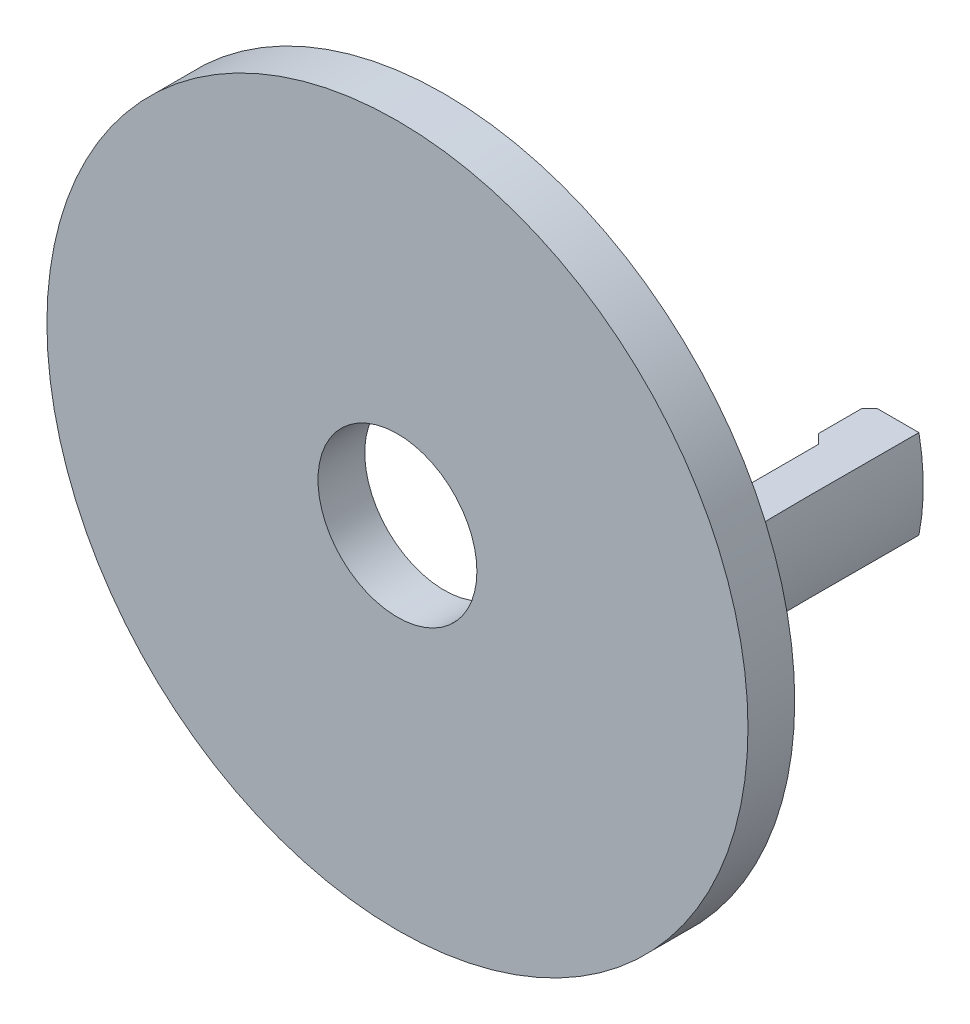
SolidWorks part; units mm, degrees
ref_plane "Front" through (0, 0, 0) normal (0, 0, 1) x (1, 0, 0)
ref_plane "Top" through (0, 0, 0) normal (0, 1, 0) x (1, 0, 0)
ref_plane "Right" through (0, 0, 0) normal (1, 0, 0) x (0, 0, -1)
sketch "Guard base sketch" plane through (0, 0, 0) normal (0, 0, 1) x (1, 0, 0)
  circle A0 centre (0, 0) radius 37.5
  dimension "D1" = 75
extrude "Guard" add sketch "Guard base sketch" along normal blind 5
sketch "Inner axle base sketch" plane through (0, 0, 5) normal (0, 0, 1) x (1, 0, 0)
  circle A0 centre (0, 0) radius 8.5
  dimension "D1" = 17
extrude "Inner axle hole" cut sketch "Inner axle base sketch" against normal through all
sketch "Coupling tooth base sketch" plane through (0, 0, 0) normal (0, 1, 0) x (1, 0, 0)
  line L0 (19.5, 0) -> (26, 0) construction
  line L1 (26, 0) -> (26, 27) construction
  line L2 (26, 0) -> (16.5, 0)
  line L3 (26, 27) -> (19.5, 27) construction
  line L4 (19.5, 27) -> (18, 25.5) construction
  line L5 (18, 21) -> (19.5, 19.5) construction
  line L6 (19.5, 19.5) -> (19.5, 0) construction
  line L7 (19.75, 20.3107) -> (19.75, 2.8964)
  line L8 (19.5, 3) -> (16.5, 0) construction
  line L9 (19.75, 20.3107) -> (18.75, 21.3107)
  line L10 (18, 25.5) -> (18, 21) construction
  line L11 (18.75, 21.3107) -> (18.75, 25.8964)
  line L12 (26, 0) -> (26, 26.75)
  line L13 (8.5, 0) -> (-8.5, 0) construction
  line L14 (19.75, 2.8964) -> (16.8536, 0)
  line L15 (18.75, 25.8964) -> (19.6036, 26.75)
  line L16 (19.6036, 26.75) -> (26, 26.75)
  line L17 (24.5, 26.5113) -> (24.5, 41.0721) construction
  line L18 (24.5, 12.4795) -> (24.5, 18.7128) construction
  line L19 (26, 0) -> (37.5, 0)
  line L20 (37.5, 0) -> (37.5, 26.75)
  line L21 (37.5, 26.75) -> (26, 26.75)
  spline S0 degree 3 poles (24.5, 26.75) (24.5, 22.7282) (24.4901, 20.5425) (24.5119, 14.9424) (24.2749, 4.9839) (26, 0) knots 0 0 0 0 0.446605 0.546605 1 1 1 1
  dimension "D1" = 135
  dimension "D2" = 9.5
  dimension "D3" = 8
  dimension "D4" = 27
  dimension "D5" = 7.5
  dimension "D6" = 0.25
  dimension "D7" = 0.25
  dimension "D8" = 0.25
  dimension "D9" = 0.75
  dimension "D10" = 1.5
  dimension "D11" = 225
  dimension "D12" = 0.25
  dimension "D13" = 1.5
  dimension "D14" = 0.75
  dimension "D15" = 26
extrude "Coupling tooth" add sketch "Coupling tooth base sketch" along normal blind 4.75 and the other way blind 4.75 contours S0 L16 L15 L11 L9 L7 L14 L2 region at (22.0194, 0, -13.0102)
ref_axis "Center Z" through (0, 0, 0) along (0, 0, -1)
revolve "Circularity cut" cut sketch "Sketch6<4>" angle 360 about axis through (0, 0, 0) along (0, 0, -1) region at (25.2982, 0, -14.9997) region at (31.75, 0, -13.375)
sketch "Sketch6<4>" plane through (0, 0, 0) normal (0, 1, 0) x (1, 0, 0) same geometry as "Coupling tooth base sketch"
mirror "Coupling teeth" about plane through (0, 0, 0) normal (1, 0, 0) of "Coupling tooth", "Circularity cut"
equation "\"mate_room\"= 0.25"
equation "\"D6@Coupling tooth base sketch\"=\"mate_room\""
equation "\"D8@Coupling tooth base sketch\"=\"mate_room\""
equation "\"D7@Coupling tooth base sketch\"=\"mate_room\""
equation "\"removal_room\"= 0.75"
equation "\"D9@Coupling tooth base sketch\"=\"removal_room\""
equation "\"D12@Coupling tooth base sketch\"=\"mate_room\""
equation "\"D14@Coupling tooth base sketch\"=\"removal_room\""
equation "\"small_inner_axle_diameter\"=17"
equation "\"D1@Inner axle base sketch\"=\"small_inner_axle_diameter\""
equation "\"large_inner_axle_diameter\"=20"
equation "\"guard_thickness\"=5"
equation "\"spool_inner_diameter_room\"=1"
equation "\"53_55_spool_inner_diameter\"=53"
equation "\"53_55_spool_thickness\"=55"
equation "\"53_55_guard_diameter\"=75"
equation "\"53_55_coupling_tooth_height\"=27"
equation "\"53_55_coupling_tooth_thickness_total\"=8"
equation "\"53_55_coupling_tooth_protrusion\"=1.5"
equation "\"53_55_coupling_tooth_head_height\"=7.5"
equation "\"53_55_coupling_tooth_depth\"=10"
equation "\"D1@Guard base sketch\"=\"53_55_guard_diameter\""
equation "\"D1@Guard\"=\"guard_thickness\""
equation "\"D4@Coupling tooth base sketch\"=\"53_55_coupling_tooth_height\""
equation "\"53_55_coupling_tooth_base_thickness\"=9.5"
equation "\"D2@Coupling tooth base sketch\"=\"53_55_coupling_tooth_base_thickness\""
equation "\"D3@Coupling tooth base sketch\"=\"53_55_coupling_tooth_thickness_total\""
equation "\"D5@Coupling tooth base sketch\"=\"53_55_coupling_tooth_head_height\""
equation "\"D10@Coupling tooth base sketch\"=\"53_55_coupling_tooth_protrusion\""
equation "\"D1@Coupling tooth\"=\"53_55_coupling_tooth_depth\"/2 - \"mate_room\""
equation "\"D2@Coupling tooth\"=\"53_55_coupling_tooth_depth\"/2 - \"mate_room\""
equation "\"D15@Coupling tooth base sketch\"=(\"53_55_spool_inner_diameter\" - \"spool_inner_diameter_room\")/2"
